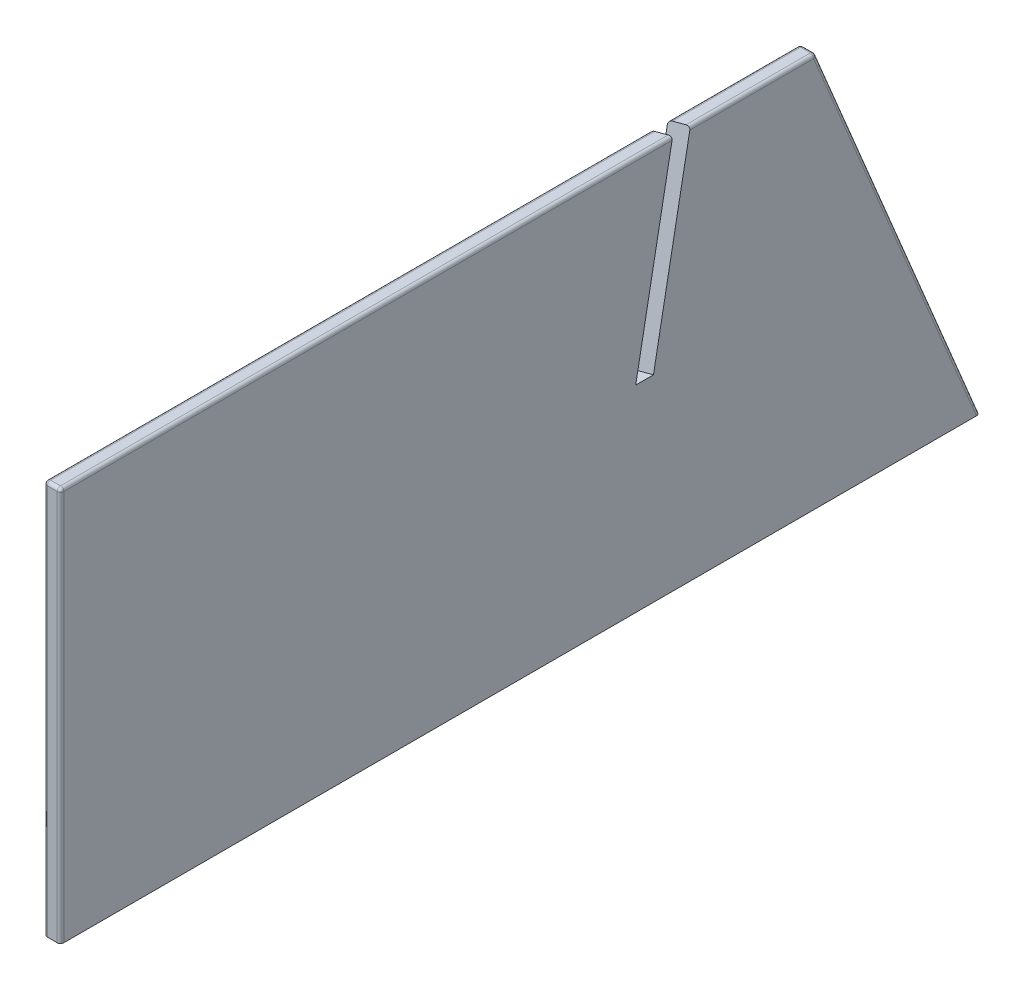
SolidWorks part; units mm, degrees
ref_plane "Front Plane" through (0, 0, 0) normal (0, 0, 1) x (1, 0, 0)
ref_plane "Top Plane" through (0, 0, 0) normal (0, 1, 0) x (1, 0, 0)
ref_plane "Right Plane" through (0, 0, 0) normal (1, 0, 0) x (0, 0, -1)
sketch "Sketch1" plane through (0, 0, 0) normal (1, 0, 0) x (0, 0, -1)
  line L0 (495.3, 304.8) -> (468.4278, 152.4)
  line L1 (0, 0) -> (711.2, 0)
  line L2 (0, 0) -> (0, 304.8)
  line L3 (0, 304.8) -> (711.2, 304.8)
  line L4 (711.2, 0) -> (711.2, 304.8)
  line L5 (468.4278, 152.4) -> (455.5319, 152.4)
  line L6 (455.5319, 152.4) -> (482.4041, 304.8)
  line L7 (482.4041, 304.8) -> (495.3, 304.8)
  line L8 (455.5319, 152.4) -> (455.5319, 304.8) construction
  line L9 (711.2, 0) -> (584.2, 304.8)
  line L10 (584.2, 304.8) -> (711.2, 304.8)
  line L11 (711.2, 0) -> (711.2, 304.8)
  dimension "D1" = 711.2
  dimension "D2" = 304.8
  dimension "D3" = 152.4
  dimension "D4" = 10
  dimension "D5" = 12.7
  dimension "D6" = 215.9
  dimension "D7" = 127
extrude "Boss-Extrude2" add sketch "Sketch1" along normal blind 12.7 contours L8 L1 L9 L3 L0 L5 | L1 L8 L3 L2 | L8 L6 L3 | L7 L0 L5 L6 region at (0, 145.4663, -321.8799) region at (0, 254, -464.4893)
ref_axis "Axis1" through (0, 0, 0) along (0, 1, 0)
ref_plane "Plane1" through (0, 0, 0) normal (0.9397, 0, -0.342) x (0, 1, 0)
sketch "Sketch3" plane through (0, 0, 0) normal (0.9397, 0, -0.342) x (0, 1, 0)
  line L0 (304.8, -453.4957) -> (152.4, -426.6234)
  line L1 (152.4, -426.6234) -> (152.4, -413.7275)
  line L2 (152.4, -413.7275) -> (304.8, -440.5997)
  line L3 (304.8, -440.5997) -> (304.8, -453.4957)
  line L4 (304.8, 0) -> (304.8, -548.9684) construction
  line L5 (0, 0) -> (304.8, 0) construction
  point P2 (228.6, -427.1636)
  point P5 (152.4, -420.1755)
  dimension "D1" = 12.7
  dimension "D2" = 152.4
  dimension "D3" = 0
  dimension "D4" = 453.4957
  dimension "D5" = 10
extrude "Cut-Extrude1" cut sketch "Sketch3" along normal through all contours L2 L3 L0 L1
fillet "Fillet1" radius 2.54 10 edges at (12.7, 152.4, 0) (0, 152.4, 0) (6.35, 304.8, 0) (0, 304.8, -234.4382) (12.7, 304.8, -236.7494) (12.7, 152.4, -647.7) (6.35, 304.8, -584.2) (0, 152.4, -647.7) (12.7, 304.8, -535.7112) (0, 304.8, -533.4)
